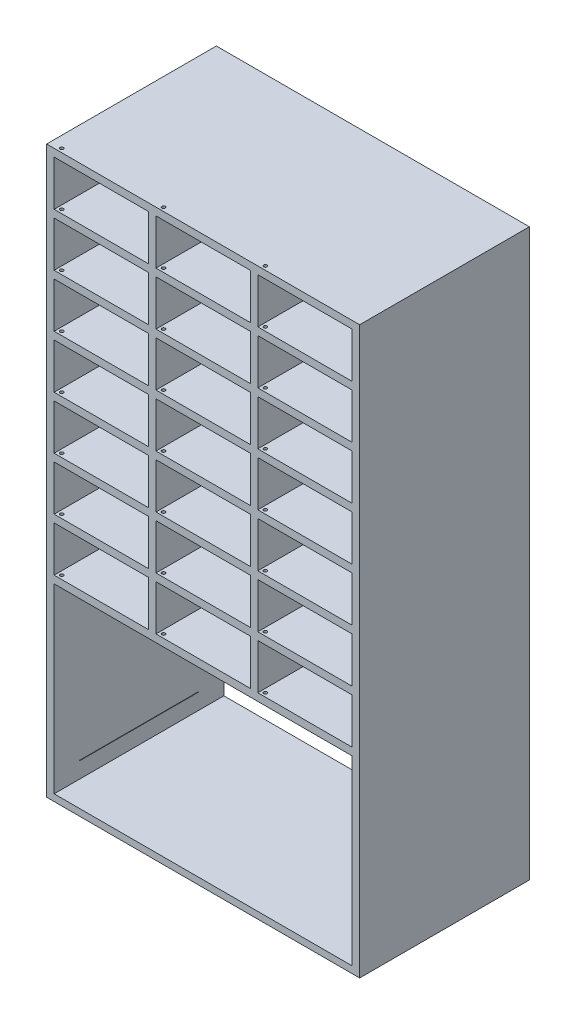
SolidWorks part; units mm, degrees
ref_plane "Front Plane" through (0, 0, 0) normal (0, 0, 1) x (1, 0, 0)
ref_plane "Top Plane" through (0, 0, 0) normal (0, 1, 0) x (1, 0, 0)
ref_plane "Right Plane" through (0, 0, 0) normal (1, 0, 0) x (0, 0, -1)
sketch "Sketch1" plane through (0, 0, 0) normal (0, 1, 0) x (1, 0, 0)
  line L1 (-280, 225) -> (280, 225)
  line L2 (-280, 225) -> (-280, -225)
  line L3 (-280, -225) -> (280, -225)
  line L4 (280, 225) -> (280, -225)
  line L5 (-280, 225) -> (280, -225) construction
  line L6 (-280, -225) -> (280, 225) construction
  point P0 (0, 0)
  dimension "D1" = 560
  dimension "D2" = 450
extrude "Boss-Extrude1" add sketch "Sketch1" along normal blind 20
sketch "Sketch3" plane through (0, 20, 0) normal (0, 1, 0) x (1, 0, 0)
  line L0 (-260, 225) -> (-260, -225)
  line L1 (280, 225) -> (-280, 225) construction
  line L2 (-280, -225) -> (280, -225) construction
  line L3 (-280, 225) -> (-280, -225) construction
  line L4 (-10, 225) -> (-10, -225)
  line L5 (10, 225) -> (10, -225)
  line L6 (260, 225) -> (260, -225)
  line L7 (280, -225) -> (280, 225) construction
  line L8 (-280, 225) -> (280, 225)
  line L9 (-280, 225) -> (-280, -225)
  line L10 (-280, -225) -> (280, -225)
  line L11 (280, -225) -> (280, 225)
  line M5 (280, -225) -> (280, 225)
  line M6 (280, 225) -> (-280, 225)
  line M7 (-280, 225) -> (-280, -225)
  line M8 (-280, -225) -> (280, -225)
  dimension "D1" = 20
  dimension "D2" = 270
  dimension "D3" = 250
  dimension "D4" = 250
  dimension "D5" = 20
extrude "Boss-Extrude2" add sketch "Sketch3" along normal blind 120 contours L0 M6 M7 M8 | L5 L4 M6 M8 | L6 M6 M8 M5
pattern_linear "LPattern2" count 7 spacing 140 along (0, 1, 0) of "Boss-Extrude1", "Boss-Extrude2"
pattern_linear "LPattern5" count 2 spacing 270 along (1, 0, 0) count 14 spacing 140 along (0, 1, 0) of "Boss-Extrude1"
sketch "Sketch6" plane through (550, 0, 0) normal (1, 0, 0) x (0, 0, -1)
  line L1 (-225, 1000) -> (225, 1000)
  line L2 (-225, 1000) -> (-225, 0)
  line L3 (-225, 0) -> (225, 0)
  line L4 (225, 1000) -> (225, 0)
extrude "Boss-Extrude5" add sketch "Sketch6" against normal blind 20
sketch "Sketch9" plane through (0, 0, 225) normal (0, 0, 1) x (1, 0, 0)
  line L0 (-260, 0) -> (-260, -482.1016)
  line L1 (-280, 0) -> (550, 0)
  line L2 (-280, 0) -> (-280, -500)
  line L3 (-280, -500) -> (550, -500)
  line L4 (550, 0) -> (550, -500)
  line L5 (-260, -482.1016) -> (530, -482.1016)
  line L6 (530, -482.1016) -> (530, 0)
  line L7 (-280, 0) -> (550, 0)
  dimension "D1" = 500
extrude "Boss-Extrude6" add sketch "Sketch9" against normal up to surface (450 mm away) contours L6 L5 L0 L1 L2 L3 L4 up to face at (405, 80, -225)
sketch "Sketch10" plane through (0, 860, 0) normal (0, 1, 0) x (1, 0, 0)
  line L0 (-280, 225) -> (-280, -225) construction
  line L1 (-280, -225) -> (550, -225) construction
  circle A0 centre (-250, -215) radius 4.4
  dimension "D2" = 8.8
  dimension "D1" = 30
  dimension "D3" = 10
extrude "Cut-Extrude1" cut sketch "Sketch10" along normal up to surface and the other way up to surface up to face at (135, 1000, 0) other way up to face at (135, 0, 0)
pattern_linear "LPattern6" count 3 spacing 270 along (1, 0, 0) of "Cut-Extrude1"
sketch "Sketch13" plane through (-280, 0, 0) normal (-1, 0, 0) x (0, 0, 1)
  line L0 (-157.5, -440) -> (157.5, -440)
  line L1 (157.5, -440) -> (157.5, -438.8)
  line L2 (157.5, -438.8) -> (-157.5, -438.8)
  line L3 (-157.5, -438.8) -> (-157.5, -440)
  line L4 (-225, -500) -> (225, -500) construction
  point P2 (0, -500)
  point P9 (0, -440)
  dimension "D1" = 1.2
  dimension "D2" = 315
  dimension "D3" = 60
extrude "Cut-Extrude3" cut sketch "Sketch13" against normal up to surface (20 mm away) up to face at (-260, -241.0508, 0)
